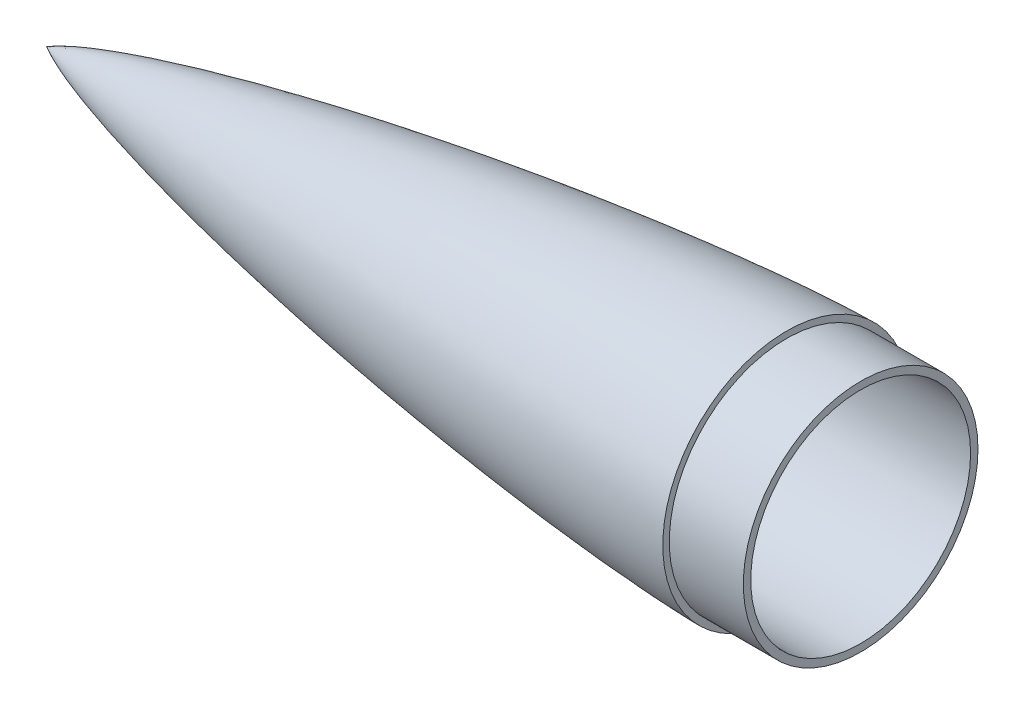
SolidWorks part; units mm, degrees
ref_plane "Front Plane" through (0, 0, 0) normal (0, 0, 1) x (1, 0, 0)
ref_plane "Top Plane" through (0, 0, 0) normal (0, 1, 0) x (1, 0, 0)
ref_plane "Right Plane" through (0, 0, 0) normal (1, 0, 0) x (0, 0, -1)
sketch "Sketch1" plane through (0, 0, 0) normal (0, 1, 0) x (1, 0, 0)
  line L3 (-55, 0) -> (55, 0) construction
  line L4 (200, 33.4356) -> (200, 0)
  line L5 (200, 0) -> (0, 0)
  spline S0 degree 4 poles (0, 0) (0.0297, 0.0027) (0.089, 0.0128) (0.1752, 0.0408) (0.3046, 0.0915) (0.5495, 0.204) (0.9043, 0.3864) (1.5855, 0.7376) (2.7098, 1.2836) (4.4238, 2.0401) (7.065, 3.0857) (10.7984, 4.4109) (16.1615, 6.1222) (23.7399, 8.2919) (33.2254, 10.7239) (44.2444, 13.2746) (56.1293, 15.7818) (68.0528, 18.0982) (80.0071, 20.2486) (91.9875, 22.2489) (103.9905, 24.1086) (116.0136, 25.8328) (128.0552, 27.4233) (140.114, 28.8776) (152.1891, 30.1899) (164.2801, 31.3479) (176.3866, 32.3324) (186.1546, 32.954) (193.5759, 33.2951) (197.9667, 33.411) (199.3222, 33.4323) (200, 33.4356) knots 0 0 0 0 0 0.000585 0.001182 0.001773 0.002733 0.005878 0.009023 0.016834 0.027293 0.042687 0.064838 0.094675 0.13791 0.197585 0.25726 0.316935 0.37661 0.436285 0.495959 0.555634 0.615309 0.674984 0.734659 0.794334 0.854008 0.913683 0.973358 0.986679 1 1 1 1 1 construction
  spline S1 degree 4 poles (0, 0) (0.0297, 0.0027) (0.089, 0.0128) (0.1752, 0.0408) (0.3046, 0.0915) (0.5495, 0.204) (0.9043, 0.3864) (1.5855, 0.7376) (2.7098, 1.2836) (4.4238, 2.0401) (7.065, 3.0857) (10.7984, 4.4109) (16.1615, 6.1222) (23.7399, 8.2919) (33.2254, 10.7239) (44.2444, 13.2746) (56.1293, 15.7818) (68.0528, 18.0982) (80.0071, 20.2486) (91.9875, 22.2489) (103.9905, 24.1086) (116.0136, 25.8328) (128.0552, 27.4233) (140.114, 28.8776) (152.1891, 30.1899) (164.2801, 31.3479) (176.3866, 32.3324) (186.1546, 32.954) (193.5759, 33.2951) (197.9667, 33.411) (199.3222, 33.4323) (200, 33.4356) knots 0 0 0 0 0 0.000585 0.001182 0.001773 0.002733 0.005878 0.009023 0.016834 0.027293 0.042687 0.064838 0.094675 0.13791 0.197585 0.25726 0.316935 0.37661 0.436285 0.495959 0.555634 0.615309 0.674984 0.734659 0.794334 0.854008 0.913683 0.973358 0.986679 1 1 1 1 1
  dimension "D1" = 200
revolve "Cone shape" add sketch "Sketch1" angle 360 about L5
shell "Shell" thickness 1.75 removed face at (200, 0, -33.4356)
sketch "Sketch2" plane through (200, 0, 0) normal (1, 0, 0) x (0, 0, -1)
  circle A0 centre (0, 0) radius 31.6855 construction
  circle A1 centre (0, 0) radius 31.6855
  circle A2 centre (0, 0) radius 29.6855
  dimension "D1" = 2
extrude "Body tube insert" add sketch "Sketch2" against normal up to next and the other way blind 20
